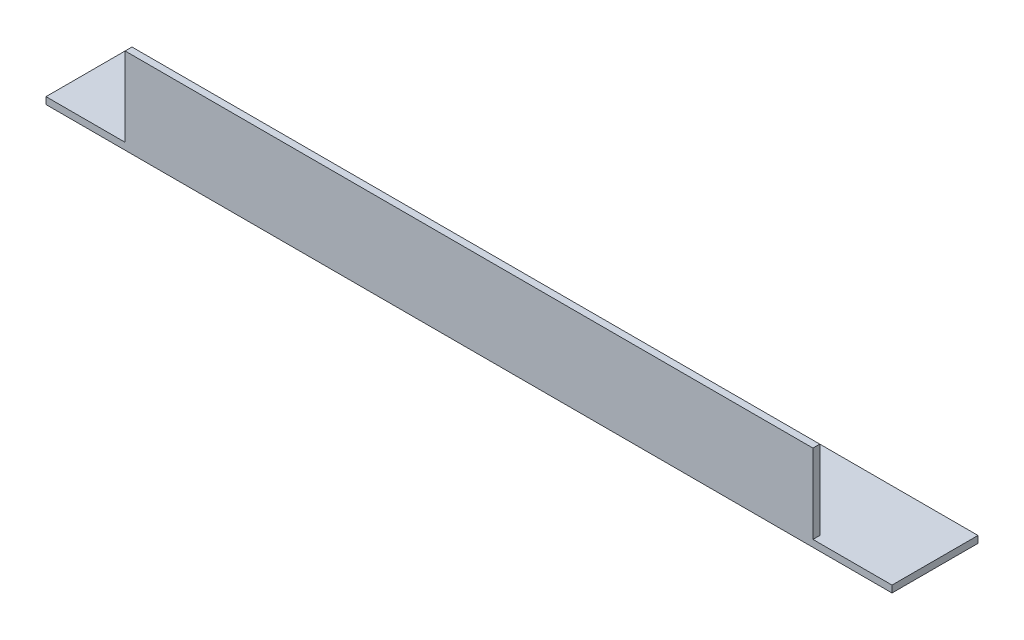
SolidWorks part; units mm, degrees
ref_plane "Спереди" through (0, 0, 0) normal (0, 0, 1) x (1, 0, 0)
ref_plane "Сверху" through (0, 0, 0) normal (0, 1, 0) x (1, 0, 0)
ref_plane "Справа" through (0, 0, 0) normal (1, 0, 0) x (0, 0, -1)
sketch "Эскиз1" plane through (0, 0, 0) normal (1, 0, 0) x (0, 0, -1)
  line L0 (0, 25) -> (0, 0)
  line L1 (0, 0) -> (25, 0)
extrude "Вытянуть-Тонкостенный1" add sketch "Эскиз1" along normal blind 246 thin thin type one direction reverse wall 2
sketch "Эскиз2" plane through (0, 0, 0) normal (0, 0, 1) x (1, 0, 0)
  line L1 (246, 25) -> (223, 25)
  line L2 (246, 25) -> (246, 2)
  line L3 (246, 2) -> (223, 2)
  line L4 (223, 25) -> (223, 2)
  line L6 (246, 25) -> (0, 25) construction
  line L7 (246, 25) -> (246, 0) construction
  line L8 (123, 31.8521) -> (123, -7.3957) construction
  line L9 (23, 25) -> (23, 2)
  line L10 (0, 2) -> (23, 2)
  line L11 (0, 25) -> (0, 2)
  line L12 (0, 25) -> (23, 25)
  dimension "D2" = 23
extrude "Вырез-Вытянуть1" cut sketch "Эскиз2" against normal through all
